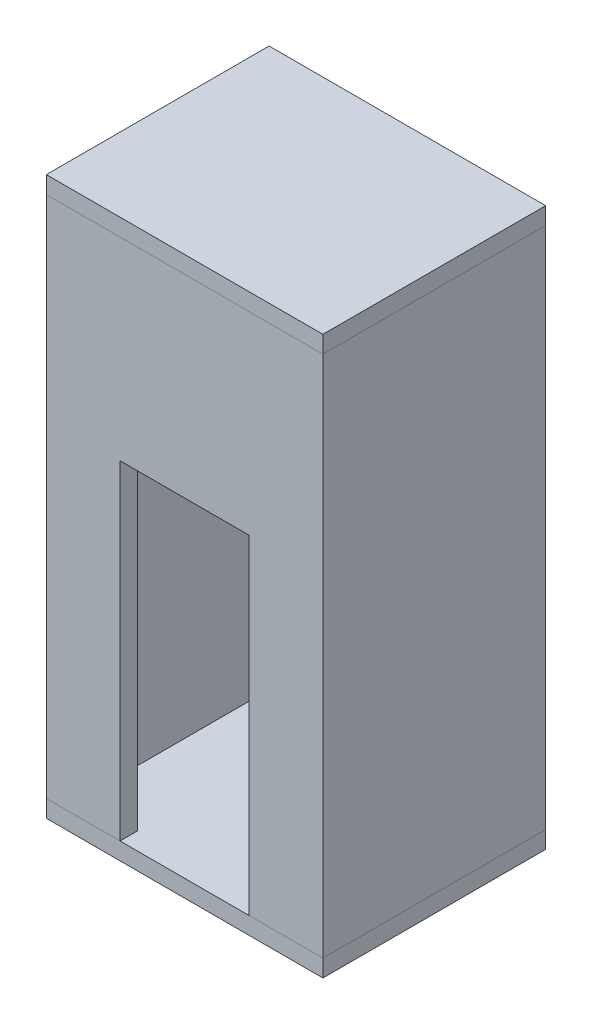
SolidWorks part; units mm, degrees
ref_plane "Front" through (0, 0, 0) normal (0, 0, 1) x (1, 0, 0)
ref_plane "Top" through (0, 0, 0) normal (0, 1, 0) x (1, 0, 0)
ref_plane "Right" through (0, 0, 0) normal (1, 0, 0) x (0, 0, -1)
sketch "Sketch1" plane through (0, 0, 0) normal (0, 1, 0) x (1, 0, 0)
  line L0 (-714.375, 555.625) -> (714.375, 555.625)
  line L1 (-815.975, -657.225) -> (815.975, -657.225)
  line L2 (-815.975, -657.225) -> (-815.975, 657.225)
  line L3 (-815.975, 657.225) -> (815.975, 657.225)
  line L4 (815.975, -657.225) -> (815.975, 657.225)
  line L5 (-815.975, -657.225) -> (815.975, 657.225) construction
  line L6 (-815.975, 657.225) -> (815.975, -657.225) construction
  line L7 (714.375, -555.625) -> (714.375, 555.625)
  line L8 (-714.375, -555.625) -> (714.375, -555.625)
  line L9 (-714.375, -555.625) -> (-714.375, 555.625)
  point P0 (0, 0)
  dimension "D1" = 1314.45
  dimension "D2" = 1631.95
  dimension "D3" = 101.6
extrude "Boss-Extrude1" add sketch "Sketch1" along normal blind 3086.1
sketch "Sketch2" plane through (0, 3086.1, 0) normal (0, 1, 0) x (1, 0, 0)
  line L4 (815.975, -657.225) -> (815.975, 657.225)
  line L5 (815.975, 657.225) -> (-815.975, 657.225)
  line L6 (-815.975, 657.225) -> (-815.975, -657.225)
  line L7 (-815.975, -657.225) -> (815.975, -657.225)
  line L8 (815.975, -657.225) -> (815.975, 657.225)
  line L9 (815.975, 657.225) -> (-815.975, 657.225)
  line L10 (-815.975, 657.225) -> (-815.975, -657.225)
  line L11 (-815.975, -657.225) -> (815.975, -657.225)
  dimension "D1" = 0
extrude "Boss-Extrude2" add sketch "Sketch2" along normal blind 101.6 separate body
sketch "Sketch3" plane through (0, 0, 657.225) normal (0, 0, 1) x (1, 0, 0)
  line L0 (-815.975, 0) -> (815.975, 0) construction
  line L1 (-381, 0) -> (381, 0)
  line L2 (-381, 0) -> (-381, 1943.1)
  line L3 (-381, 1943.1) -> (381, 1943.1)
  line L4 (381, 0) -> (381, 1943.1)
  line L5 (0, 1943.1) -> (0, 0) construction
  dimension "D1" = 1943.1
  dimension "D2" = 762
extrude "Cut-Extrude1" cut sketch "Sketch3" against normal up to next (101.6 mm away)
sketch "Sketch4" plane through (0, 0, 0) normal (0, -1, 0) x (1, 0, 0)
  line L1 (-815.975, -657.225) -> (815.975, -657.225)
  line L2 (-815.975, -657.225) -> (-815.975, 657.225)
  line L3 (-815.975, 657.225) -> (815.975, 657.225)
  line L4 (815.975, -657.225) -> (815.975, 657.225)
  line L5 (-815.975, -657.225) -> (815.975, 657.225) construction
  line L6 (-815.975, 657.225) -> (815.975, -657.225) construction
  point P0 (0, 0)
extrude "Boss-Extrude3" add sketch "Sketch4" along normal blind 101.6 separate body
sketch "Sketch5" plane through (0, 0, -555.625) normal (0, 0, 1) x (1, 0, 0)
  line L4 (-714.375, 0) -> (714.375, 0)
  line L5 (714.375, 0) -> (714.375, 3086.1)
  line L6 (714.375, 3086.1) -> (-714.375, 3086.1)
  line L7 (-714.375, 3086.1) -> (-714.375, 0)
  line L8 (-714.375, 0) -> (714.375, 0)
  line L9 (714.375, 0) -> (714.375, 3086.1)
  line L10 (714.375, 3086.1) -> (-714.375, 3086.1)
  line L11 (-714.375, 3086.1) -> (-714.375, 0)
  dimension "D1" = 0
extrude "Cut-Extrude2" cut sketch "Sketch5" against normal through all
